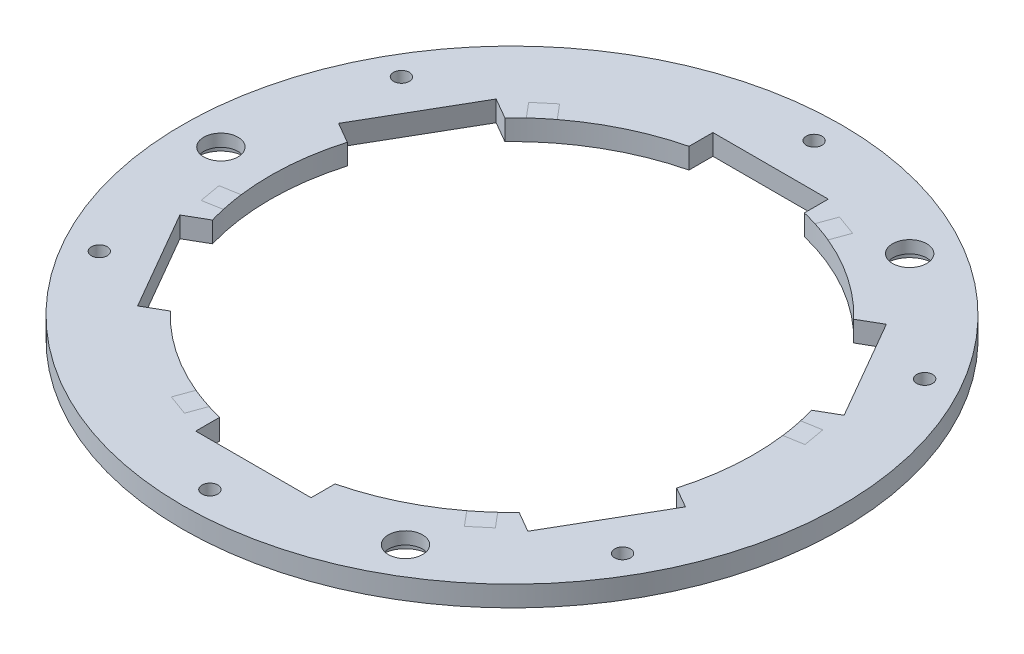
SolidWorks part; units mm, degrees
material "6061 Alloy"
ref_plane "Front Plane" through (0, 0, 0) normal (0, 0, 1) x (1, 0, 0)
ref_plane "Top Plane" through (0, 0, 0) normal (0, 1, 0) x (1, 0, 0)
ref_plane "Right Plane" through (0, 0, 0) normal (1, 0, 0) x (0, 0, -1)
sketch "Sketch1" plane through (0, 0, 0) normal (0, 1, 0) x (1, 0, 0)
  line L0 (-13.335, -54.2656) -> (-13.335, -58.1814)
  line L1 (13.335, -54.2656) -> (13.335, -58.1814)
  line L2 (-13.335, -59.7901) -> (13.335, -59.7901)
  line L3 (13.335, -58.1814) -> (13.335, -59.7901)
  line L4 (-13.335, -58.1814) -> (-13.335, -59.7901)
  line L5 (0, 0) -> (-67.31, 0) construction
  line L6 (0, 0) -> (0, -23.1086) construction
  circle A0 centre (0, 0) radius 55.88
  circle A1 centre (0, 0) radius 76.2
  circle A2 centre (0, 0) radius 59.69
  circle A3 centre (0, -69.85) radius 1.8288
  circle A4 centre (-67.31, 0) radius 3.9561
  dimension "D1" = 111.76
  dimension "D2" = 152.4
  dimension "D8" = 3.6576
  dimension "D11" = 7.9121
  dimension "D4" = 13.335
  dimension "D5" = 13.335
  dimension "D7" = 69.85
  dimension "D6" = 5.5245
  dimension "D9" = 67.31
  dimension "D10" = 90
  dimension "D3" = 3.81
extrude "Boss-Extrude1" add sketch "Sketch1" along normal blind 4.7625 contours L1 A2 L0 A0 | A1 A2 A0 region at (-15.0127, 0, 56.2235) region at (-74.0447, 0, 0)
pattern_circular "CirPattern1" count 6 over 360 about axis through (0, 4.7625, 0) along (0, 1, 0) of face at (-13.335, 2.3813, 57.0278) of face at (13.335, 2.3813, 57.0278) of face at (0, 4.7625, 71.6788) of face at (0, 2.3813, 59.7901)
sketch "Sketch2" plane through (0, 0, 0) normal (1, 0, 0) x (0, 0, -1)
  line L0 (76.2, 4.7625) -> (-76.2, 4.7625) construction
  line L1 (-76.2, 0) -> (76.2, 0) construction
  line L2 (76.2, 4.7625) -> (-76.2, 4.7625)
  line L3 (-76.2, 0) -> (76.2, 0)
  line L4 (0, 0) -> (0, 4.7625) construction
  circle A0 centre (-75.2856, 0) radius 2.667
  dimension "D1" = 5.334
  dimension "D2" = 0.9144
revolve "Cut-Revolve1" [suppressed] cut sketch "Sketch2" angle 360 about L4
sketch "Sketch4" plane through (0, 0, 0) normal (0, -1, 0) x (1, 0, 0)
  line L0 (0, 0) -> (-67.31, 0) construction
  line L1 (0, 0) -> (0, -39.7137) construction
  circle A0 centre (-67.31, 0) radius 5.588
  circle A2 centre (-67.31, 0) radius 3.9561 construction
  circle A3 centre (-67.31, 0) radius 3.9561
  dimension "D2" = 11.176
extrude "Cut-Extrude1" cut sketch "Sketch4" against normal blind 1.905 contours A0 region at (-72.7399, 0, 0)
pattern_circular "CirPattern2" count 3 over 360 about axis through (0, 0, 0) along (0, 1, 0) of face at (-67.31, 4.7625, 3.956) of face at (-67.31, 1.905, -3.9561) of face at (-67.31, 1.905, -5.588)
sketch "Sketch5" plane through (0, 4.7625, 0) normal (0, 1, 0) x (1, 0, 0)
  line L0 (0, 0) -> (-20.0894, -55.1952)
  line L1 (0, 0) -> (0, -18.6852)
  line L2 (-16.5968, -53.0258) -> (-18.2257, -57.5011)
  line L3 (-18.2257, -57.5011) -> (-22.9993, -55.7636)
  line L4 (-22.9993, -55.7636) -> (-21.3704, -51.2884)
  line L5 (-59.7924, -7.9638) -> (-55.1022, -7.1368)
  line L6 (-54.2201, -12.1397) -> (-58.9103, -12.9667)
  line L7 (-58.9103, -12.9667) -> (-59.7924, -7.9638)
  line L8 (-36.7931, 47.7998) -> (-33.7318, 44.1515)
  line L9 (-37.6233, 40.8862) -> (-40.6846, 44.5345)
  line L10 (-40.6846, 44.5345) -> (-36.7931, 47.7998)
  line L11 (22.9993, 55.7636) -> (21.3704, 51.2884)
  line L12 (16.5968, 53.0258) -> (18.2257, 57.5011)
  line L13 (18.2257, 57.5011) -> (22.9993, 55.7636)
  line L14 (59.7924, 7.9638) -> (55.1022, 7.1368)
  line L15 (54.2201, 12.1397) -> (58.9103, 12.9667)
  line L16 (58.9103, 12.9667) -> (59.7924, 7.9638)
  line L17 (36.7931, -47.7998) -> (33.7318, -44.1515)
  line L18 (37.6233, -40.8862) -> (40.6846, -44.5345)
  line L19 (40.6846, -44.5345) -> (36.7931, -47.7998)
  circle A0 centre (0, 0) radius 55.5625
  circle A1 centre (0, 0) radius 58.7375 construction
  circle A2 centre (0, 0) radius 55.5625
  circle A3 centre (0, 0) radius 55.5625
  circle A4 centre (0, 0) radius 55.5625
  circle A5 centre (0, 0) radius 55.5625
  circle A6 centre (0, 0) radius 55.5625
  point P38 (0, 0)
  dimension "D1" = 111.125
  dimension "D3" = 20
  dimension "D4" = 2.54
  dimension "D5" = 4.7625
  dimension "D6" = 2.54
  dimension "D2" = 3.175
  dimension "D7" = 6
split line "Split Line1"
equation "\"Middle Coupler Inner Daimeter\"= 3.875in"
equation "\"Middle Coupler  Wall Thickness\" = 0.25in"
equation "\"Middle Coupler Bottom Thickness\"= 0.2in"
equation "\"Bearing Rail Offset\"= 0.45in"
equation "\"3-56 UNF Tap\"= 0.089in"
equation "\"3-56 UNF Clearance\"= 0.104in"
equation "\"Ball Bearing Distance\"= 0.03in"
equation "\"D1@Sketch1\"=\"Middle Coupler Inner Daimeter\"+0.5+0.0125*2in"
equation "\"TCA Outer Diameter\" = 6in"
equation "\"D2@Sketch1\"=\"TCA Outer Diameter\""
equation "\"D4@Sketch1\"=0.50 + (0.05/2)"
equation "\"D5@Sketch1\"=\"D4@Sketch1\""
equation "\"D7@Sketch1\"=(\"D2@Sketch1\"-0.5)/2"
equation "\"D8@Sketch1\"=\"6-32 Clearance\""
equation "\"D2@Sketch2\"=\"Interstage Aeroframe Wall Thickness\"/2"
equation "\"Interstage Aeroframe Wall Thickness\" = 0.072in"
equation "\"Compression Spring OD\"= 0.42in"
equation "\"10-24 Tap\"= 0.157in"
equation "\"10-24 Clearance\"= 0.196in"
equation "\"D2@Sketch4\"=\"Compression Spring OD\"+0.02"
equation "\"D3@Sketch1\"=0.125in+(0.05/2)"
equation "\"Lower Stage Fuselage Wall Thickness\" = 0.25in"
equation "\"6-32 Tap\" = 0.107in"
equation "\"1/4-20 Tap\" = 0.201in"
equation "\"3-48 Tap\"= 0.079in"
equation "\"12-24 Tap\" = 0.177in"
equation "\"3-48 Clearance\" = 0.104in"
equation "\"6-32 Clearance\" = 0.144"
equation "\"D6@Sketch1\"=3/16 + 0.03"
equation "\"D9@Sketch1\"=(\"D2@Sketch1\"+\"D1@Sketch1\")/4+0.05"
equation "\"D11@Sketch1\"=5/16in - 0.001in"
equation "\"D1@Sketch5\"=\"Middle Coupler Inner Daimeter\"+0.5"
equation "\"D5@Sketch5\"=3/16"
equation "\"D6@Sketch5\"=\"D4@Sketch5\""
equation "\"D1@Boss-Extrude1\"=3/16"
